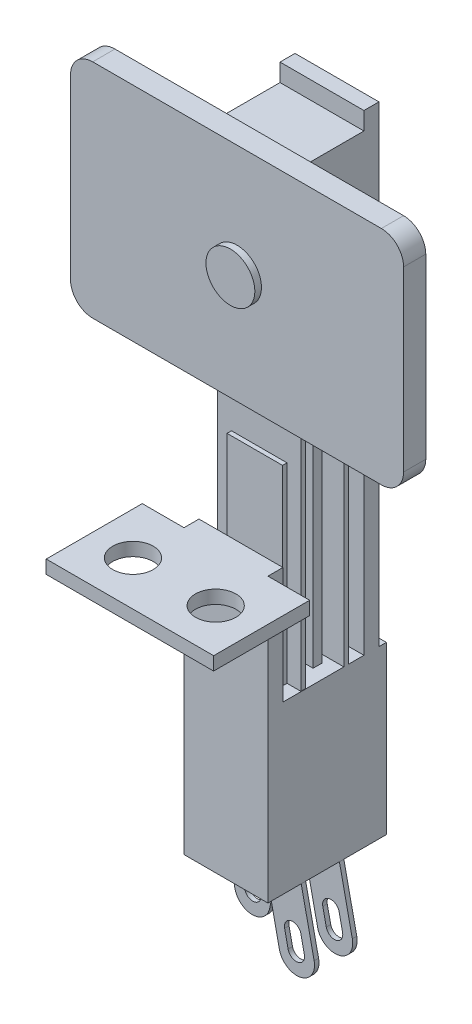
SolidWorks part; units mm, degrees
ref_plane "Front Plane" through (0, 0, 0) normal (0, 0, 1) x (1, 0, 0)
ref_plane "Top Plane" through (0, 0, 0) normal (0, 1, 0) x (1, 0, 0)
ref_plane "Right Plane" through (0, 0, 0) normal (1, 0, 0) x (0, 0, -1)
sketch "Sketch2" plane through (0, 0, 0) normal (0, 1, 0) x (1, 0, 0)
  line L0 (0, 10.9855) -> (0, 0) construction
  line L1 (-9.5758, 0) -> (9.5758, 0)
  line L2 (-9.5758, 0) -> (-9.5758, 10.9855)
  line L3 (-9.5758, 10.9855) -> (9.5758, 10.9855)
  line L4 (9.5758, 0) -> (9.5758, 10.9855)
  circle A0 centre (-4.7308, 5.08) radius 2.3177
  circle A1 centre (4.7307, 5.08) radius 2.3177
  point P4 (0, 0)
  dimension "D3" = 4.6355
  dimension "D1" = 19.1516
  dimension "D2" = 10.9855
  dimension "D4" = 9.4615
  dimension "D5" = 5.08
extrude "Boss-Extrude1" add sketch "Sketch2" against normal blind 1.524
sketch "Sketch3" plane through (0, 0, 0) normal (0, 1, 0) x (1, 0, 0)
  line L0 (9.5758, 10.9855) -> (-9.5758, 10.9855) construction
  line L1 (-4.8006, 10.9855) -> (4.8006, 10.9855)
  line L2 (-4.8006, 10.9855) -> (-4.8006, 12.7)
  line L3 (-4.8006, 12.7) -> (4.8006, 12.7)
  line L4 (4.8006, 10.9855) -> (4.8006, 12.7)
  line L5 (-9.5758, 0) -> (9.5758, 0) construction
  point P7 (0, 10.9855)
  point P8 (0, 10.9855)
  dimension "D1" = 9.6012
  dimension "D2" = 12.7
extrude "Boss-Extrude2" add sketch "Sketch3" against normal blind 32.385
sketch "Sketch4" plane through (0, 0, -12.7) normal (0, 0, -1) x (-1, 0, 0)
  line L0 (4.8006, -32.385) -> (4.8006, 0) construction
  line L1 (-4.8006, -32.385) -> (4.8006, -32.385)
  line L2 (-4.8006, -32.385) -> (-4.8006, -13.335)
  line L3 (-4.8006, -13.335) -> (4.8006, -13.335)
  line L4 (4.8006, -32.385) -> (4.8006, -13.335)
  dimension "D1" = 19.05
extrude "Boss-Extrude3" add sketch "Sketch4" along normal blind 9.271 separate body
sketch "Sketch5" plane through (0, 0, -21.971) normal (0, 0, -1) x (-1, 0, 0)
  line L0 (4.8006, -32.385) -> (4.8006, -13.335) construction
  line L1 (-4.8006, -32.385) -> (4.8006, -32.385)
  line L2 (-4.8006, -32.385) -> (-4.8006, 40.64)
  line L3 (-4.8006, 40.64) -> (4.8006, 40.64)
  line L4 (4.8006, -32.385) -> (4.8006, 40.64)
  dimension "D1" = 73.025
extrude "Boss-Extrude4" add sketch "Sketch5" along normal blind 1.7145 separate body
sketch "Sketch6" plane through (0, 0, -23.6855) normal (0, 0, -1) x (-1, 0, 0)
  line L0 (4.8006, -32.385) -> (4.8006, 40.64) construction
  line L1 (-4.8006, -32.385) -> (4.8006, -32.385)
  line L2 (-4.8006, -32.385) -> (-4.8006, -13.335)
  line L3 (-4.8006, -13.335) -> (4.8006, -13.335)
  line L4 (4.8006, -32.385) -> (4.8006, -13.335)
extrude "Boss-Extrude5" add sketch "Sketch6" along normal blind 0.8509 separate body
ref_plane "Plane1" through (0, 0, -14.2875) normal (0, 0, -1) x (-1, 0, 0)
ref_plane "Plane2" through (0, 0, -14.7955) normal (0, 0, -1) x (-1, 0, 0)
ref_plane "Plane3" through (0, 0, -17.78) normal (0, 0, -1) x (-1, 0, 0)
ref_plane "Plane4" through (0, 0, -19.6723) normal (0, 0, -1) x (-1, 0, 0)
sketch "Sketch7" plane through (0, 0, -14.2875) normal (0, 0, -1) x (-1, 0, 0)
  line L0 (4.8006, -13.335) -> (-4.8006, -13.335) construction
  line L1 (-3.175, -13.335) -> (3.175, -13.335)
  line L2 (-3.175, -13.335) -> (-3.175, 8.509)
  line L3 (-3.175, 8.509) -> (3.175, 8.509)
  line L4 (3.175, -13.335) -> (3.175, 8.509)
  point P6 (0, -13.335)
  point P7 (0, -13.335)
  dimension "D1" = 21.844
  dimension "D2" = 6.35
extrude "Boss-Extrude6" add sketch "Sketch7" along normal up to surface (0.508 mm away) up to plane "Plane2"
sketch "Sketch8" plane through (0, 0, -14.7955) normal (0, 0, -1) x (-1, 0, 0)
  line L0 (-3.175, -13.335) -> (3.175, -13.335) construction
  line L1 (4.7625, -13.335) -> (-4.7625, -13.335)
  line L2 (4.7625, -13.335) -> (4.7625, 20.066)
  line L3 (4.7625, 20.066) -> (-4.7625, 20.066) construction
  line L4 (-4.7625, -13.335) -> (-4.7625, 20.066)
  line L5 (4.8006, 40.64) -> (-4.8006, 40.64) construction
  arc A0 (4.7625, 20.066) -> (-4.7625, 20.066) centre (0, 26.9636) ccw
  point P7 (0, -13.335)
  point P8 (0, -13.335)
  point P13 (0, 40.64)
  dimension "D3" = 16.764
  dimension "D1" = 33.401
  dimension "D2" = 9.525
extrude "Boss-Extrude7" add sketch "Sketch8" along normal blind 0.508 separate body
sketch "Sketch9" plane through (0, 0, -17.78) normal (0, 0, -1) x (-1, 0, 0)
  line L1 (-3.175, -13.335) -> (3.175, -13.335)
  line L2 (-3.175, -13.335) -> (-3.175, 18.415)
  line L3 (-3.175, 18.415) -> (3.175, 18.415)
  line L4 (3.175, -13.335) -> (3.175, 18.415)
  line L6 (3.175, 8.509) -> (-3.175, 8.509) construction
  line L7 (-4.7625, -13.335) -> (4.7625, -13.335) construction
  point P8 (0, -13.335)
  point P9 (0, -13.335)
  dimension "D1" = 31.75
extrude "Boss-Extrude8" add sketch "Sketch9" along normal blind 0.508 separate body
sketch "Sketch10" plane through (0, 0, -18.288) normal (0, 0, -1) x (-1, 0, 0)
  line L0 (-3.175, 18.415) -> (-3.175, -13.335) construction
  line L1 (-3.175, 8.509) -> (3.175, 8.509)
  line L2 (-3.175, 8.509) -> (-3.175, -13.335)
  line L3 (-3.175, -13.335) -> (3.175, -13.335)
  line L4 (3.175, 8.509) -> (3.175, -13.335)
  line L5 (-3.175, -13.335) -> (3.175, -13.335) construction
  line L6 (3.175, -13.335) -> (3.175, 18.415) construction
  dimension "D1" = 21.844
extrude "Boss-Extrude9" add sketch "Sketch10" along normal blind 0.508 separate body
sketch "Sketch11" plane through (0, 0, -19.6723) normal (0, 0, -1) x (-1, 0, 0)
  line L0 (-4.8006, 40.64) -> (-4.8006, -32.385) construction
  line L1 (-4.8006, -13.335) -> (4.8006, -13.335)
  line L2 (-4.8006, -13.335) -> (-4.8006, 18.415)
  line L3 (-4.8006, 18.415) -> (4.8006, 18.415)
  line L4 (4.8006, -13.335) -> (4.8006, 18.415)
  line L5 (4.8006, -32.385) -> (4.8006, 40.64) construction
  line L6 (-3.175, -13.335) -> (3.175, -13.335) construction
  dimension "D1" = 31.75
extrude "Boss-Extrude10" add sketch "Sketch11" along normal blind 0.508 separate body
sketch "Sketch12" plane through (0, 0, -14.7955) normal (0, 0, 1) x (1, 0, 0)
  line L1 (-16.51, 14.2636) -> (16.51, 14.2636)
  line L2 (-19.05, 16.8036) -> (-19.05, 37.1236)
  line L3 (-16.51, 39.6636) -> (16.51, 39.6636)
  line L4 (19.05, 16.8036) -> (19.05, 37.1236)
  line L5 (-19.05, 14.2636) -> (19.05, 39.6636) construction
  line L6 (-19.05, 39.6636) -> (19.05, 14.2636) construction
  arc A0 (4.7625, 20.066) -> (-4.7625, 20.066) centre (0, 26.9636) ccw construction
  arc A1 (-16.51, 14.2636) -> (-19.05, 16.8036) centre (-16.51, 16.8036) cw
  arc A2 (16.51, 14.2636) -> (19.05, 16.8036) centre (16.51, 16.8036) ccw
  arc A3 (16.51, 39.6636) -> (19.05, 37.1236) centre (16.51, 37.1236) cw
  arc A4 (-19.05, 37.1236) -> (-16.51, 39.6636) centre (-16.51, 37.1236) cw
  point P0 (0, 26.9636)
  dimension "D3" = 2.54
  dimension "D1" = 25.4
  dimension "D2" = 38.1
extrude "Boss-Extrude11" add sketch "Sketch12" along normal blind 2.54
sketch "Sketch13" plane through (0, 0, -12.2555) normal (0, 0, 1) x (1, 0, 0)
  circle A0 centre (0, 26.9636) radius 2.794
  arc A1 (4.7625, 20.066) -> (-4.7625, 20.066) centre (0, 26.9636) ccw construction
  dimension "D1" = 5.588
extrude "Boss-Extrude12" add sketch "Sketch13" along normal blind 0.762
sketch "Sketch14" plane through (0, 0, -21.971) normal (0, 0, 1) x (1, 0, 0)
  line L0 (-4.8006, -32.385) -> (-4.8006, 40.64) construction
  line L1 (-4.8006, 38.608) -> (4.8006, 38.608)
  line L2 (-4.8006, 38.608) -> (-4.8006, 19.558)
  line L3 (-4.8006, 19.558) -> (4.8006, 19.558)
  line L4 (4.8006, 38.608) -> (4.8006, 19.558)
  line L5 (4.8006, 40.64) -> (4.8006, -32.385) construction
  line L6 (-4.8006, 40.64) -> (4.8006, 40.64) construction
  dimension "D1" = 19.05
  dimension "D2" = 2.032
extrude "Boss-Extrude13" add sketch "Sketch14" along normal up to surface (6.6675 mm away) separate body up to face at (0, 7.1854, -15.3035)
sketch "Sketch15" plane through (0, 0, -14.7955) normal (0, 0, -1) x (-1, 0, 0)
  line L0 (-4.8006, -32.385) -> (-6.2793, -39.2737)
  line L1 (-6.2793, -39.2737) -> (-2.3059, -40.1267) construction
  line L2 (-2.3059, -40.1267) -> (-0.644, -32.385)
  line L3 (4.8006, -32.385) -> (-4.8006, -32.385) construction
  line L4 (-0.644, -32.385) -> (-4.8006, -32.385)
  line L5 (-4.2926, -41.7322) -> (-0.644, -41.7322) construction
  line L6 (-0.644, -41.7322) -> (-0.644, -32.385) construction
  line L7 (-6.3246, -39.7002) -> (-6.3246, -32.385) construction
  line L8 (-6.3246, -32.385) -> (-4.8006, -32.385) construction
  line L9 (0, -32.385) -> (0, -1.524) construction
  line L10 (-4.8006, -1.524) -> (4.8006, -1.524) construction
  line L11 (-4.7191, -41.6869) -> (-2.7223, -32.385) construction
  line L12 (-2.9002, -37.7519) -> (-3.3, -39.6145)
  line L13 (-3.3, -39.6145) -> (-5.1626, -39.2147) construction
  line L14 (-5.1626, -39.2147) -> (-4.7628, -37.3521)
  line L15 (-4.7628, -37.3521) -> (-2.9002, -37.7519) construction
  line L19 (4.7628, -37.3521) -> (2.9002, -37.7519) construction
  line L20 (3.3, -39.6145) -> (5.1626, -39.2147) construction
  line L21 (4.7191, -41.6869) -> (2.7223, -32.385) construction
  line L22 (6.3246, -32.385) -> (4.8006, -32.385) construction
  line L23 (6.3246, -39.7002) -> (6.3246, -32.385) construction
  line L24 (0.644, -41.7322) -> (0.644, -32.385) construction
  line L25 (4.2926, -41.7322) -> (0.644, -41.7322) construction
  line L26 (6.2793, -39.2737) -> (2.3059, -40.1267) construction
  line L27 (5.1626, -39.2147) -> (4.7628, -37.3521) construction
  line L28 (2.9002, -37.7519) -> (3.3, -39.6145) construction
  line L29 (0.644, -32.385) -> (4.8006, -32.385) construction
  line L30 (2.3059, -40.1267) -> (0.644, -32.385) construction
  line L31 (4.8006, -32.385) -> (6.2793, -39.2737) construction
  arc A0 (-6.2793, -39.2737) -> (-2.3059, -40.1267) centre (-4.2926, -39.7002) ccw
  arc A2 (-2.9002, -37.7519) -> (-4.7628, -37.3521) centre (-3.8315, -37.552) ccw
  arc A3 (-3.3, -39.6145) -> (-5.1626, -39.2147) centre (-4.2313, -39.4146) cw
  arc A4 (3.3, -39.6145) -> (5.1626, -39.2147) centre (4.2313, -39.4146) ccw construction
  arc A5 (2.9002, -37.7519) -> (4.7628, -37.3521) centre (3.8315, -37.552) cw construction
  arc A6 (6.2793, -39.2737) -> (2.3059, -40.1267) centre (4.2926, -39.7002) cw construction
  point P18 (-4.2313, -39.4146)
  point P23 (-3.8315, -37.552)
  point P26 (-3.6316, -36.6208)
  point P27 (-4.4312, -40.3459)
  dimension "D1" = 9.3472
  dimension "D2" = 1.524
  dimension "D3" = 4.064
  dimension "D4" = 3.81
  dimension "D5" = 1.905
  dimension "D6" = 1.3716
extrude "Boss-Extrude14" add sketch "Sketch15" along normal blind 0.508
sketch "Sketch17" plane through (0, 0, -18.288) normal (0, 0, -1) x (-1, 0, 0)
  line L0 (2.9002, -37.7519) -> (3.3, -39.6145) construction
  line L1 (5.1626, -39.2147) -> (4.7628, -37.3521) construction
  line L2 (4.8006, -32.385) -> (6.2793, -39.2737) construction
  line L3 (0.644, -32.385) -> (4.8006, -32.385) construction
  line L4 (2.3059, -40.1267) -> (0.644, -32.385) construction
  line L5 (2.9002, -37.7519) -> (3.3, -39.6145)
  line L6 (5.1626, -39.2147) -> (4.7628, -37.3521)
  line L7 (4.8006, -32.385) -> (6.2793, -39.2737)
  line L8 (0.644, -32.385) -> (4.8006, -32.385)
  line L9 (2.3059, -40.1267) -> (0.644, -32.385)
  arc A0 (3.3, -39.6145) -> (5.1626, -39.2147) centre (4.2313, -39.4146) ccw construction
  arc A1 (4.7628, -37.3521) -> (2.9002, -37.7519) centre (3.8315, -37.552) ccw construction
  arc A2 (2.3059, -40.1267) -> (6.2793, -39.2737) centre (4.2926, -39.7002) ccw construction
  arc A3 (3.3, -39.6145) -> (5.1626, -39.2147) centre (4.2313, -39.4146) ccw
  arc A4 (4.7628, -37.3521) -> (2.9002, -37.7519) centre (3.8315, -37.552) ccw
  arc A5 (2.3059, -40.1267) -> (6.2793, -39.2737) centre (4.2926, -39.7002) ccw
extrude "Boss-Extrude15" add sketch "Sketch17" along normal blind 0.508
sketch "Sketch18" plane through (0, 0, -19.6723) normal (0, 0, 1) x (1, 0, 0)
  line L0 (2.9002, -37.7519) -> (3.3, -39.6145) construction
  line L1 (5.1626, -39.2147) -> (4.7628, -37.3521) construction
  line L2 (4.8006, -32.385) -> (6.2793, -39.2737) construction
  line L3 (2.3059, -40.1267) -> (0.644, -32.385) construction
  line L4 (0.644, -32.385) -> (4.8006, -32.385) construction
  line L5 (2.9002, -37.7519) -> (3.3, -39.6145)
  line L6 (5.1626, -39.2147) -> (4.7628, -37.3521)
  line L7 (4.8006, -32.385) -> (6.2793, -39.2737)
  line L8 (2.3059, -40.1267) -> (0.644, -32.385)
  line L9 (0.644, -32.385) -> (4.8006, -32.385)
  arc A0 (2.3059, -40.1267) -> (6.2793, -39.2737) centre (4.2926, -39.7002) ccw construction
  arc A1 (3.3, -39.6145) -> (5.1626, -39.2147) centre (4.2313, -39.4146) ccw construction
  arc A2 (4.7628, -37.3521) -> (2.9002, -37.7519) centre (3.8315, -37.552) ccw construction
  arc A3 (2.3059, -40.1267) -> (6.2793, -39.2737) centre (4.2926, -39.7002) ccw
  arc A4 (3.3, -39.6145) -> (5.1626, -39.2147) centre (4.2313, -39.4146) ccw
  arc A5 (4.7628, -37.3521) -> (2.9002, -37.7519) centre (3.8315, -37.552) ccw
extrude "Boss-Extrude16" add sketch "Sketch18" along normal blind 0.508
sketch "Sketch19" plane through (0, 0, -24.5364) normal (0, 0, -1) x (-1, 0, 0)
  line L0 (4.8006, -13.335) -> (-4.8006, -13.335) construction
  line L1 (-4.8006, -22.86) -> (4.8006, -22.86) construction
  line L3 (-4.8006, -13.335) -> (-4.8006, -32.385) construction
  line L4 (4.8006, -32.385) -> (4.8006, -13.335) construction
  circle A0 centre (0, -17.9387) radius 2.794
  circle A1 centre (0, -27.7812) radius 2.794
  point P7 (0, -13.335)
  dimension "D1" = 5.588
  dimension "D2" = 9.8425
extrude "Boss-Extrude17" add sketch "Sketch19" along normal blind 0.8382
combine bodies "Combine1" operation type add bodies to combine 102 104 105 108 109 110 112 113 116 117 118
